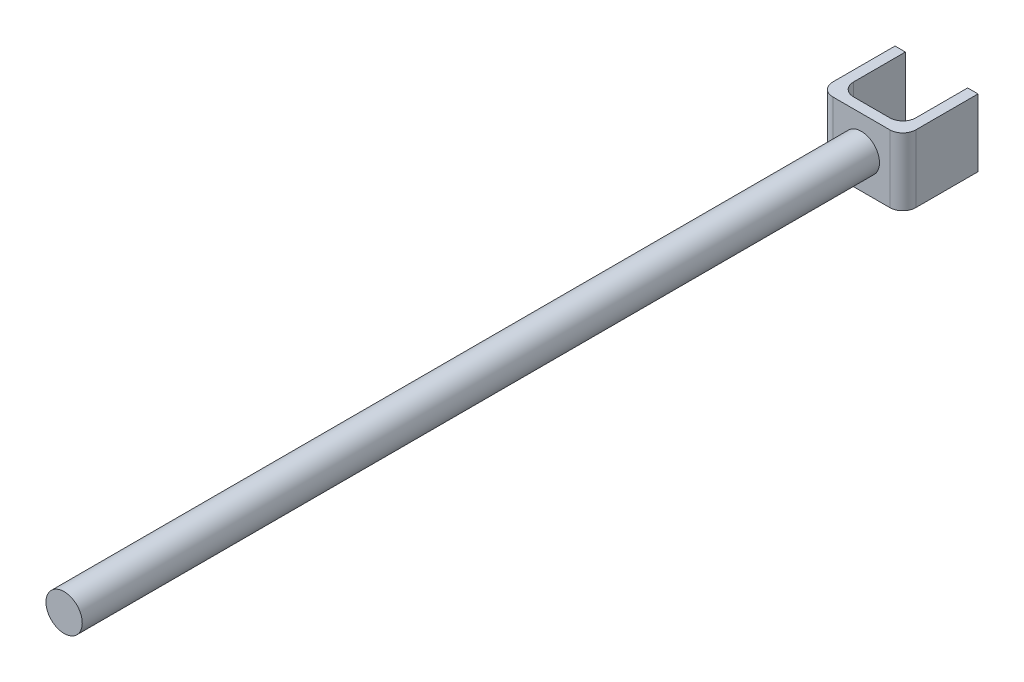
SolidWorks part; units mm, degrees
ref_plane "Front Plane" through (0, 0, 0) normal (0, 0, 1) x (1, 0, 0)
ref_plane "Top Plane" through (0, 0, 0) normal (0, 1, 0) x (1, 0, 0)
ref_plane "Right Plane" through (0, 0, 0) normal (1, 0, 0) x (0, 0, -1)
sketch "Sketch1" plane through (0, 0, 0) normal (0, 1, 0) x (1, 0, 0)
  line L0 (0, 0) -> (0, -20.7763) construction
  line L1 (7, -20.7763) -> (-7, -20.7763)
  line L2 (12, -15.7763) -> (12, 4.2237)
  line L3 (12, 4.2237) -> (16, 4.2237)
  line L4 (16, 4.2237) -> (16, -19.7763)
  line L5 (11, -24.7763) -> (-11, -24.7763)
  line L6 (-16, 4.2237) -> (-16, -19.7763)
  line L7 (-12, 4.2237) -> (-16, 4.2237)
  line L8 (-12, -15.7763) -> (-12, 4.2237)
  arc A0 (16, -19.7763) -> (11, -24.7763) centre (11, -19.7763) cw
  arc A1 (7, -20.7763) -> (12, -15.7763) centre (7, -15.7763) ccw
  arc A2 (-7, -20.7763) -> (-12, -15.7763) centre (-7, -15.7763) cw
  arc A3 (-16, -19.7763) -> (-11, -24.7763) centre (-11, -19.7763) ccw
  point P6 (0, -20.7763)
  point P13 (12, -20.7763)
  point P20 (0, -24.7763)
  point P22 (-12, -20.7763)
  dimension "D5" = 5
  dimension "D1" = 4
  dimension "D2" = 4
  dimension "D3" = 25
  dimension "D4" = 12
extrude "Boss-Extrude1" add sketch "Sketch1" along normal blind 13 and the other way blind 13
sketch "Sketch2" plane through (0, 0, 24.7763) normal (0, 0, 1) x (1, 0, 0)
  circle A0 centre (0, 0) radius 7
  dimension "D1" = 14
extrude "Boss-Extrude2" add sketch "Sketch2" along normal blind 307.5
sketch "Sketch3" plane through (0, 0, 0) normal (0, 1, 0) x (1, 0, 0)
  line L0 (0, 0) -> (0, -400) construction
  point P4 (0, -400)
  point P5 (0, 0)
  dimension "D1" = 400
